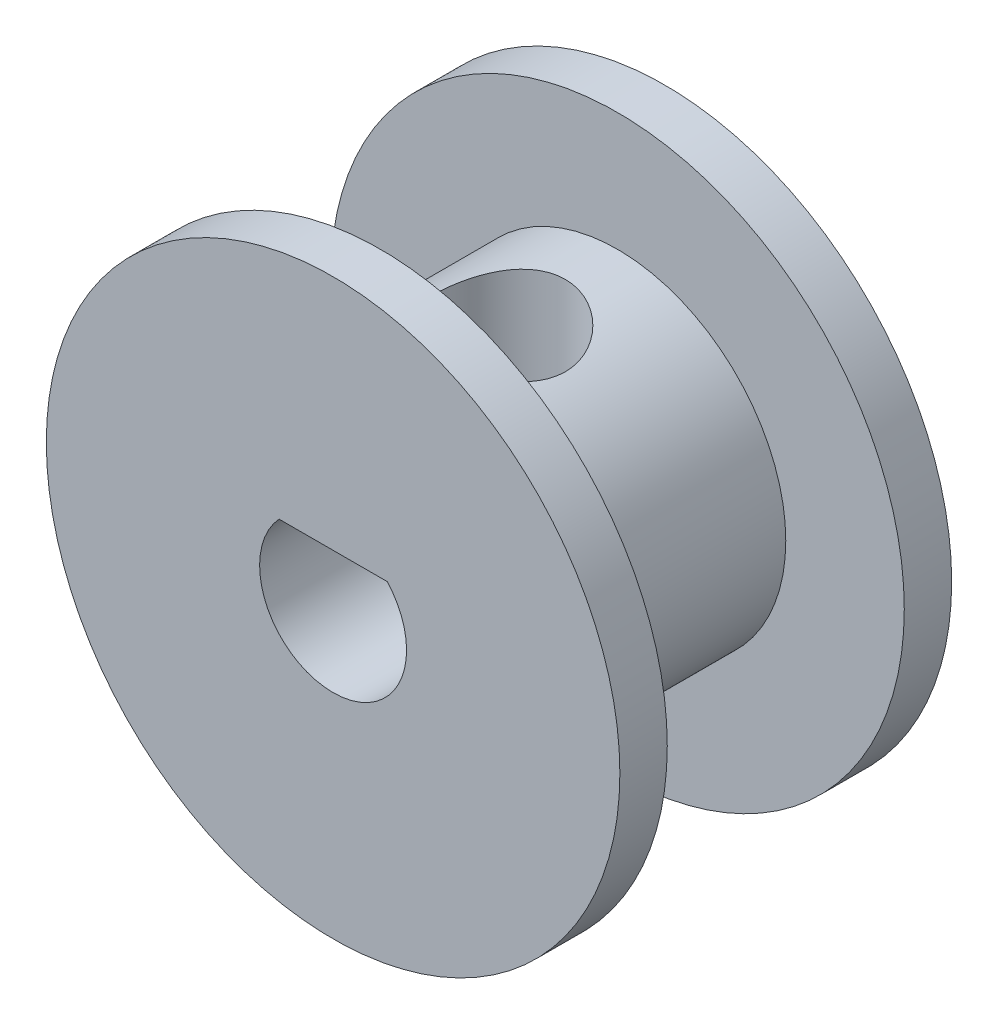
SolidWorks part; units mm, degrees
ref_plane "Front Plane" through (0, 0, 0) normal (0, 0, 1) x (1, 0, 0)
ref_plane "Top Plane" through (0, 0, 0) normal (0, 1, 0) x (1, 0, 0)
ref_plane "Right Plane" through (0, 0, 0) normal (1, 0, 0) x (0, 0, -1)
sketch "Sketch2" plane through (0, 0, 0) normal (1, 0, 0) x (0, 0, -1)
  line L0 (0, 1.55) -> (0, 6.05)
  line L1 (0, 6.05) -> (1, 6.05)
  line L2 (1, 6.05) -> (1, 3.55)
  line L3 (1, 3.55) -> (6, 3.55)
  line L4 (6, 3.55) -> (6, 6.05)
  line L5 (6, 6.05) -> (7, 6.05)
  line L6 (7, 6.05) -> (7, 1.55)
  line L7 (7, 1.55) -> (0, 1.55)
  line L8 (-2.1414, 0) -> (12.0517, 0) construction
  dimension "D1" = 1.55
  dimension "D2" = 7
  dimension "D3" = 1
  dimension "D4" = 1
  dimension "D5" = 2
  dimension "D6" = 4.5
revolve "Revolve1" add sketch "Sketch2" angle 360 about L8
sketch "Sketch4" plane through (0, 0, 0) normal (0, 0, 1) x (1, 0, 0)
  line L0 (-1.1402, 1.05) -> (1.1402, 1.05)
  circle A0 centre (0, 0) radius 1.55 construction
  circle A3 centre (0, 0) radius 1.55
  point P4 (0, -1.55)
  circle M4 centre (0, 0) radius 1.55
  dimension "D1" = 2.6
extrude "Boss-Extrude1" add sketch "Sketch4" against normal up to surface (7 mm away) contours L0 M4 region at (0, 1.2531, 0) up to face at (6.05, 0, -7)
sketch "Sketch5" plane through (0, 1.05, 0) normal (0, -1, 0) x (1, 0, 0)
  circle A0 centre (0, -3.5) radius 1.4
  dimension "D1" = 2.8
  dimension "D2" = 3.5
extrude "Cut-Extrude1" cut sketch "Sketch5" against normal through all both and the other way through all
